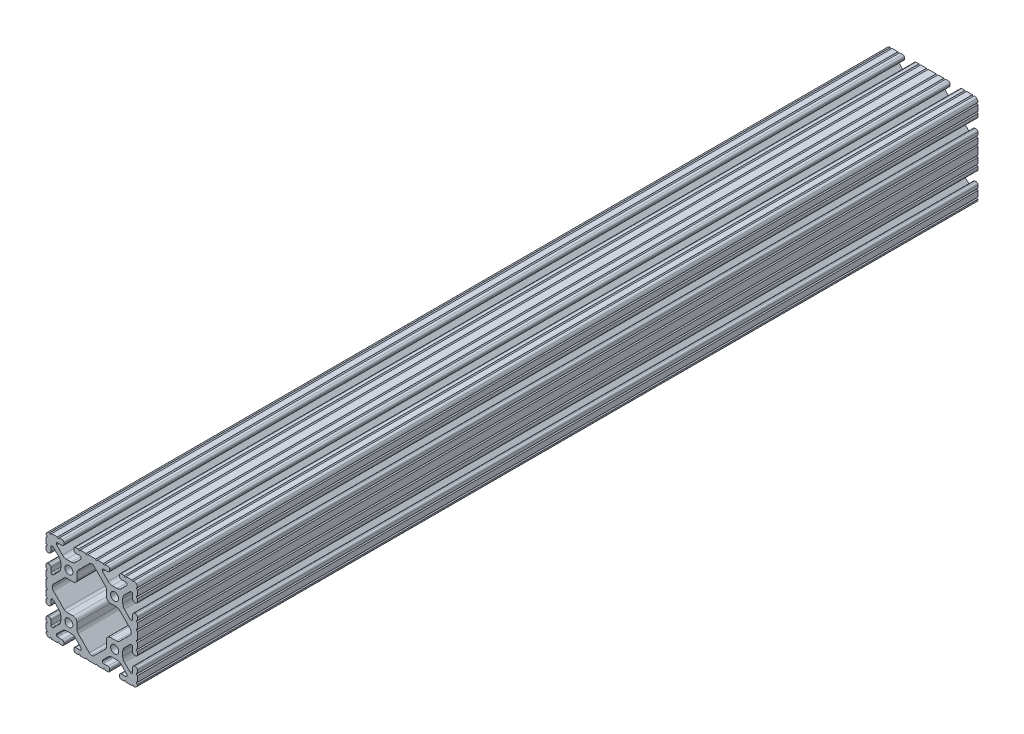
SolidWorks part; units mm, degrees
ref_plane "Front Plane" through (0, 0, 0) normal (0, 0, 1) x (1, 0, 0)
ref_plane "Top Plane" through (0, 0, 0) normal (0, 1, 0) x (1, 0, 0)
ref_plane "Right Plane" through (0, 0, 0) normal (1, 0, 0) x (0, 0, -1)
sketch "Sketch1" plane through (0, 0, 0) normal (0, 0, 1) x (1, 0, 0)
  line L0 (0, 38.1) -> (0, -38.1) construction
  line L1 (-38.1, -38.1) -> (38.1, -38.1) construction
  line L2 (-38.1, -38.1) -> (-38.1, 38.1) construction
  line L3 (-38.1, 38.1) -> (38.1, 38.1) construction
  line L4 (38.1, -38.1) -> (38.1, 38.1) construction
  line L5 (0, 38.1) -> (0, -38.1) construction
  line L6 (-38.1, 0) -> (38.1, 0) construction
  line L7 (-19.05, 19.05) -> (19.05, 19.05) construction
  line L8 (-19.05, 19.05) -> (-19.05, -19.05) construction
  line L9 (-19.05, -19.05) -> (19.05, -19.05) construction
  line L10 (19.05, 19.05) -> (19.05, -19.05) construction
  line L11 (-23.114, 38.1) -> (-23.114, -38.1) construction
  line L12 (-23.114, -38.1) -> (-14.986, 38.1) construction
  line L13 (-14.986, 38.1) -> (-14.986, -38.1) construction
  circle A0 centre (19.05, 19.05) radius 3.3274
  point P0 (0, 0)
  point P9 (0, 0)
  point P12 (-19.05, 0)
  line B0 (-11.3637, -22.8433) -> (-2.0515, -32.1555)
  line B1 (-12.2936, -15.4686) -> (-12.2936, -20.5983)
  line B2 (-20.769, -12.2936) -> (-15.4686, -12.2936)
  line B3 (-31.9021, -2.4756) -> (-23.0141, -11.3637)
  line B4 (-23.0141, 11.3637) -> (-31.9021, 2.4756)
  line B5 (-15.4686, 12.2936) -> (-20.769, 12.2936)
  line B6 (-12.2936, 20.5983) -> (-12.2936, 15.4686)
  line B7 (-2.0515, 32.1555) -> (-11.3637, 22.8433)
  line B8 (11.3637, 22.8433) -> (2.0515, 32.1555)
  line B9 (12.2936, 15.4686) -> (12.2936, 20.5983)
  line B10 (20.769, 12.2936) -> (15.4686, 12.2936)
  line B11 (31.9021, 2.4756) -> (23.0141, 11.3637)
  line B12 (23.0141, -11.3637) -> (31.9021, -2.4756)
  line B13 (15.4686, -12.2936) -> (20.769, -12.2936)
  line B14 (12.2936, -20.5983) -> (12.2936, -15.4686)
  line B15 (2.0515, -32.1555) -> (11.3637, -22.8433)
  line B16 (-4.7773, 38.1) -> (-9.6053, 38.1)
  line B17 (-11.1289, 38.1) -> (-13.4112, 38.1)
  line B18 (-14.986, 36.5252) -> (-14.986, 35.6108)
  line B19 (-13.4112, 34.036) -> (-9.652, 34.036)
  line B20 (-8.763, 33.147) -> (-8.763, 32.4935)
  line B21 (-9.0234, 31.8649) -> (-13.6907, 27.1976)
  line B22 (-17.0493, 25.8064) -> (-21.0507, 25.8064)
  line B23 (-24.4093, 27.1976) -> (-29.1002, 31.8885)
  line B24 (-29.337, 32.7207) -> (-29.337, 33.147)
  line B25 (-28.448, 34.036) -> (-24.6888, 34.036)
  line B26 (-23.114, 35.6108) -> (-23.114, 36.5252)
  line B27 (-24.6888, 38.1) -> (-27.0772, 38.1)
  line B28 (-28.6011, 38.1) -> (-33.4288, 38.1)
  line B29 (-38.1, 33.373) -> (-38.1, 28.5453)
  line B30 (-38.1, 27.0238) -> (-38.1, 24.6302)
  line B31 (-36.5252, 23.0554) -> (-35.6108, 23.0554)
  line B32 (-34.036, 24.6302) -> (-34.036, 28.448)
  line B33 (-33.147, 29.337) -> (-32.6643, 29.337)
  line B34 (-32.0357, 29.0766) -> (-27.1976, 24.2385)
  line B35 (-25.8064, 20.8799) -> (-25.8064, 17.2201)
  line B36 (-27.1976, 13.8615) -> (-31.9489, 9.1101)
  line B37 (-32.7869, 8.763) -> (-33.0603, 8.763)
  line B38 (-34.036, 9.7387) -> (-34.036, 13.4698)
  line B39 (-35.6108, 15.0446) -> (-36.5252, 15.0446)
  line B40 (-38.1, 13.4698) -> (-38.1, 11.075)
  line B41 (-38.1, 9.552) -> (-38.1, 4.7238)
  line B42 (-38.1, 3.2007) -> (-38.1, -3.2007)
  line B43 (-38.1, -4.7238) -> (-38.1, -9.552)
  line B44 (-38.1, -11.075) -> (-38.1, -13.4698)
  line B45 (-36.5252, -15.0446) -> (-35.6108, -15.0446)
  line B46 (-34.036, -13.4698) -> (-34.036, -9.7387)
  line B47 (-33.0603, -8.763) -> (-32.7869, -8.763)
  line B48 (-31.9489, -9.1101) -> (-27.1976, -13.8615)
  line B49 (-25.8064, -17.2201) -> (-25.8064, -20.8799)
  line B50 (-27.1976, -24.2385) -> (-32.0357, -29.0766)
  line B51 (-32.6643, -29.337) -> (-33.147, -29.337)
  line B52 (-34.036, -28.448) -> (-34.036, -24.6302)
  line B53 (-35.6108, -23.0554) -> (-36.5252, -23.0554)
  line B54 (-38.1, -24.6302) -> (-38.1, -27.0238)
  line B55 (-38.1, -28.5453) -> (-38.1, -33.373)
  line B56 (-33.4288, -38.1) -> (-28.6011, -38.1)
  line B57 (-27.0772, -38.1) -> (-24.6888, -38.1)
  line B58 (-23.114, -36.5252) -> (-23.114, -35.6108)
  line B59 (-24.6888, -34.036) -> (-28.448, -34.036)
  line B60 (-29.337, -33.147) -> (-29.337, -32.7207)
  line B61 (-29.1002, -31.8885) -> (-24.4093, -27.1976)
  line B62 (-21.0507, -25.8064) -> (-17.0493, -25.8064)
  line B63 (-13.6907, -27.1976) -> (-9.0234, -31.8649)
  line B64 (-8.763, -32.4935) -> (-8.763, -33.147)
  line B65 (-9.652, -34.036) -> (-13.4112, -34.036)
  line B66 (-14.986, -35.6108) -> (-14.986, -36.5252)
  line B67 (-13.4112, -38.1) -> (-11.1289, -38.1)
  line B68 (-9.6053, -38.1) -> (-4.7773, -38.1)
  line B69 (-3.2537, -38.1) -> (3.2537, -38.1)
  line B70 (4.7773, -38.1) -> (9.6053, -38.1)
  line B71 (11.1289, -38.1) -> (13.4112, -38.1)
  line B72 (14.986, -36.5252) -> (14.986, -35.6108)
  line B73 (13.4112, -34.036) -> (9.652, -34.036)
  line B74 (8.763, -33.147) -> (8.763, -32.4935)
  line B75 (9.0234, -31.8649) -> (13.6907, -27.1976)
  line B76 (17.0493, -25.8064) -> (21.0507, -25.8064)
  line B77 (24.4093, -27.1976) -> (29.1002, -31.8885)
  line B78 (29.337, -32.7207) -> (29.337, -33.147)
  line B79 (28.448, -34.036) -> (24.6888, -34.036)
  line B80 (23.114, -35.6108) -> (23.114, -36.5252)
  line B81 (24.6888, -38.1) -> (27.0772, -38.1)
  line B82 (28.6011, -38.1) -> (33.4288, -38.1)
  line B83 (38.1, -33.373) -> (38.1, -28.5453)
  line B84 (38.1, -27.0238) -> (38.1, -24.6302)
  line B85 (36.5252, -23.0554) -> (35.6108, -23.0554)
  line B86 (34.036, -24.6302) -> (34.036, -28.448)
  line B87 (33.147, -29.337) -> (32.6643, -29.337)
  line B88 (32.0357, -29.0766) -> (27.1976, -24.2385)
  line B89 (25.8064, -20.8799) -> (25.8064, -17.2201)
  line B90 (27.1976, -13.8615) -> (31.9489, -9.1101)
  line B91 (32.7869, -8.763) -> (33.0603, -8.763)
  line B92 (34.036, -9.7387) -> (34.036, -13.4698)
  line B93 (35.6108, -15.0446) -> (36.5252, -15.0446)
  line B94 (38.1, -13.4698) -> (38.1, -11.075)
  line B95 (38.1, -9.552) -> (38.1, -4.7238)
  line B96 (38.1, -3.2007) -> (38.1, 3.2007)
  line B97 (38.1, 4.7238) -> (38.1, 9.552)
  line B98 (38.1, 11.075) -> (38.1, 13.4698)
  line B99 (36.5252, 15.0446) -> (35.6108, 15.0446)
  line B100 (34.036, 13.4698) -> (34.036, 9.7387)
  line B101 (33.0603, 8.763) -> (32.7869, 8.763)
  line B102 (31.9489, 9.1101) -> (27.1976, 13.8615)
  line B103 (25.8064, 17.2201) -> (25.8064, 20.8799)
  line B104 (27.1976, 24.2385) -> (32.0357, 29.0766)
  line B105 (32.6643, 29.337) -> (33.147, 29.337)
  line B106 (34.036, 28.448) -> (34.036, 24.6302)
  line B107 (35.6108, 23.0554) -> (36.5252, 23.0554)
  line B108 (38.1, 24.6302) -> (38.1, 27.0238)
  line B109 (38.1, 28.5453) -> (38.1, 33.373)
  line B110 (33.4288, 38.1) -> (28.6011, 38.1)
  line B111 (27.0772, 38.1) -> (24.6888, 38.1)
  line B112 (23.114, 36.5252) -> (23.114, 35.6108)
  line B113 (24.6888, 34.036) -> (28.448, 34.036)
  line B114 (29.337, 33.147) -> (29.337, 32.7207)
  line B115 (29.1002, 31.8885) -> (24.4093, 27.1976)
  line B116 (21.0507, 25.8064) -> (17.0493, 25.8064)
  line B117 (13.6907, 27.1976) -> (9.0234, 31.8649)
  line B118 (8.763, 32.4935) -> (8.763, 33.147)
  line B119 (9.652, 34.036) -> (13.4112, 34.036)
  line B120 (14.986, 35.6108) -> (14.986, 36.5252)
  line B121 (13.4112, 38.1) -> (11.1289, 38.1)
  line B122 (9.6053, 38.1) -> (4.7773, 38.1)
  line B123 (3.2537, 38.1) -> (-3.2537, 38.1)
  circle B124 centre (-19.05, 19.05) radius 3.3274
  circle B125 centre (-19.05, -19.05) radius 3.3274
  circle B126 centre (19.05, -19.05) radius 3.3274
  circle B127 centre (19.05, 19.05) radius 3.3274
  arc B128 (0, -33.011) -> (2.0515, -32.1555) centre (-0.0139, -30.09) ccw
  arc B129 (-2.0515, -32.1555) -> (0, -33.011) centre (0.0139, -30.09) ccw
  arc B130 (-12.2936, -20.5983) -> (-11.3637, -22.8433) centre (-9.1186, -20.5983) ccw
  arc B131 (-12.2936, -15.4686) -> (-15.4686, -12.2936) centre (-15.4686, -15.4686) ccw
  arc B132 (-23.0141, -11.3637) -> (-20.769, -12.2936) centre (-20.769, -9.1186) ccw
  arc B133 (-32.7287, 0) -> (-31.9021, -2.4756) centre (-29.8367, -0.4102) ccw
  arc B134 (-31.9021, 2.4756) -> (-32.7287, 0) centre (-29.8367, 0.4102) ccw
  arc B135 (-20.769, 12.2936) -> (-23.0141, 11.3637) centre (-20.769, 9.1186) ccw
  arc B136 (-15.4686, 12.2936) -> (-12.2936, 15.4686) centre (-15.4686, 15.4686) ccw
  arc B137 (-11.3637, 22.8433) -> (-12.2936, 20.5983) centre (-9.1186, 20.5983) ccw
  arc B138 (0, 33.011) -> (-2.0515, 32.1555) centre (0.0139, 30.09) ccw
  arc B139 (2.0515, 32.1555) -> (0, 33.011) centre (-0.0139, 30.09) ccw
  arc B140 (12.2936, 20.5983) -> (11.3637, 22.8433) centre (9.1186, 20.5983) ccw
  arc B141 (12.2936, 15.4686) -> (15.4686, 12.2936) centre (15.4686, 15.4686) ccw
  arc B142 (23.0141, 11.3637) -> (20.769, 12.2936) centre (20.769, 9.1186) ccw
  arc B143 (32.7287, 0) -> (31.9021, 2.4756) centre (29.8367, 0.4102) ccw
  arc B144 (31.9021, -2.4756) -> (32.7287, 0) centre (29.8367, -0.4102) ccw
  arc B145 (20.769, -12.2936) -> (23.0141, -11.3637) centre (20.769, -9.1186) ccw
  arc B146 (15.4686, -12.2936) -> (12.2936, -15.4686) centre (15.4686, -15.4686) ccw
  arc B147 (11.3637, -22.8433) -> (12.2936, -20.5983) centre (9.1186, -20.5983) ccw
  arc B148 (-4.7773, 38.1) -> (-3.2537, 38.1) centre (-4.0155, 38.0824) ccw
  arc B149 (-11.1289, 38.1) -> (-9.6053, 38.1) centre (-10.3671, 38.0824) ccw
  arc B150 (-13.4112, 38.1) -> (-14.986, 36.5252) centre (-13.4112, 36.5252) ccw
  arc B151 (-14.986, 35.6108) -> (-13.4112, 34.036) centre (-13.4112, 35.6108) ccw
  arc B152 (-8.763, 33.147) -> (-9.652, 34.036) centre (-9.652, 33.147) ccw
  arc B153 (-9.0234, 31.8649) -> (-8.763, 32.4935) centre (-9.652, 32.4935) ccw
  arc B154 (-17.0493, 25.8064) -> (-13.6907, 27.1976) centre (-17.0493, 30.5562) ccw
  arc B155 (-24.4093, 27.1976) -> (-21.0507, 25.8064) centre (-21.0507, 30.5562) ccw
  arc B156 (-29.337, 32.7207) -> (-29.1002, 31.8885) centre (-28.4716, 32.5172) ccw
  arc B157 (-28.448, 34.036) -> (-29.337, 33.147) centre (-28.448, 33.147) ccw
  arc B158 (-24.6888, 34.036) -> (-23.114, 35.6108) centre (-24.6888, 35.6108) ccw
  arc B159 (-23.114, 36.5252) -> (-24.6888, 38.1) centre (-24.6888, 36.5252) ccw
  arc B160 (-28.6011, 38.1) -> (-27.0772, 38.1) centre (-27.8392, 38.0824) ccw
  arc B161 (-34.9527, 38.1) -> (-33.4288, 38.1) centre (-34.1907, 38.0824) ccw
  arc B162 (-34.9527, 38.1) -> (-37.0861, 37.1826) centre (-34.8521, 34.9266) ccw
  arc B163 (-37.0861, 37.1826) -> (-38.1, 34.8455) centre (-34.925, 34.8566) ccw
  arc B164 (-38.1, 33.373) -> (-38.1, 34.8455) centre (-37.9035, 34.1092) ccw
  arc B165 (-38.1, 27.0238) -> (-38.1, 28.5453) centre (-37.9035, 27.7845) ccw
  arc B166 (-38.1, 24.6302) -> (-36.5252, 23.0554) centre (-36.5252, 24.6302) ccw
  arc B167 (-35.6108, 23.0554) -> (-34.036, 24.6302) centre (-35.6108, 24.6302) ccw
  arc B168 (-33.147, 29.337) -> (-34.036, 28.448) centre (-33.147, 28.448) ccw
  arc B169 (-32.0357, 29.0766) -> (-32.6643, 29.337) centre (-32.6643, 28.448) ccw
  arc B170 (-25.8064, 20.8799) -> (-27.1976, 24.2385) centre (-30.5562, 20.8799) ccw
  arc B171 (-27.1976, 13.8615) -> (-25.8064, 17.2201) centre (-30.5562, 17.2201) ccw
  arc B172 (-32.7869, 8.763) -> (-31.9489, 9.1101) centre (-32.7869, 9.9481) ccw
  arc B173 (-34.036, 9.7387) -> (-33.0603, 8.763) centre (-33.0603, 9.7387) ccw
  arc B174 (-34.036, 13.4698) -> (-35.6108, 15.0446) centre (-35.6108, 13.4698) ccw
  arc B175 (-36.5252, 15.0446) -> (-38.1, 13.4698) centre (-36.5252, 13.4698) ccw
  arc B176 (-38.1, 9.552) -> (-38.1, 11.075) centre (-37.9035, 10.3135) ccw
  arc B177 (-38.1, 3.2007) -> (-38.1, 4.7238) centre (-37.9035, 3.9622) ccw
  arc B178 (-38.1, -4.7238) -> (-38.1, -3.2007) centre (-37.9035, -3.9622) ccw
  arc B179 (-38.1, -11.075) -> (-38.1, -9.552) centre (-37.9035, -10.3135) ccw
  arc B180 (-38.1, -13.4698) -> (-36.5252, -15.0446) centre (-36.5252, -13.4698) ccw
  arc B181 (-35.6108, -15.0446) -> (-34.036, -13.4698) centre (-35.6108, -13.4698) ccw
  arc B182 (-33.0603, -8.763) -> (-34.036, -9.7387) centre (-33.0603, -9.7387) ccw
  arc B183 (-31.9489, -9.1101) -> (-32.7869, -8.763) centre (-32.7869, -9.9481) ccw
  arc B184 (-25.8064, -17.2201) -> (-27.1976, -13.8615) centre (-30.5562, -17.2201) ccw
  arc B185 (-27.1976, -24.2385) -> (-25.8064, -20.8799) centre (-30.5562, -20.8799) ccw
  arc B186 (-32.6643, -29.337) -> (-32.0357, -29.0766) centre (-32.6643, -28.448) ccw
  arc B187 (-34.036, -28.448) -> (-33.147, -29.337) centre (-33.147, -28.448) ccw
  arc B188 (-34.036, -24.6302) -> (-35.6108, -23.0554) centre (-35.6108, -24.6302) ccw
  arc B189 (-36.5252, -23.0554) -> (-38.1, -24.6302) centre (-36.5252, -24.6302) ccw
  arc B190 (-38.1, -28.5453) -> (-38.1, -27.0238) centre (-37.9035, -27.7845) ccw
  arc B191 (-38.1, -34.8455) -> (-38.1, -33.373) centre (-37.9035, -34.1092) ccw
  arc B192 (-38.1, -34.8455) -> (-37.0861, -37.1826) centre (-34.925, -34.8566) ccw
  arc B193 (-37.0861, -37.1826) -> (-34.9527, -38.1) centre (-34.8521, -34.9266) ccw
  arc B194 (-33.4288, -38.1) -> (-34.9527, -38.1) centre (-34.1907, -38.0824) ccw
  arc B195 (-27.0772, -38.1) -> (-28.6011, -38.1) centre (-27.8392, -38.0824) ccw
  arc B196 (-24.6888, -38.1) -> (-23.114, -36.5252) centre (-24.6888, -36.5252) ccw
  arc B197 (-23.114, -35.6108) -> (-24.6888, -34.036) centre (-24.6888, -35.6108) ccw
  arc B198 (-29.337, -33.147) -> (-28.448, -34.036) centre (-28.448, -33.147) ccw
  arc B199 (-29.1002, -31.8885) -> (-29.337, -32.7207) centre (-28.4716, -32.5172) ccw
  arc B200 (-21.0507, -25.8064) -> (-24.4093, -27.1976) centre (-21.0507, -30.5562) ccw
  arc B201 (-13.6907, -27.1976) -> (-17.0493, -25.8064) centre (-17.0493, -30.5562) ccw
  arc B202 (-8.763, -32.4935) -> (-9.0234, -31.8649) centre (-9.652, -32.4935) ccw
  arc B203 (-9.652, -34.036) -> (-8.763, -33.147) centre (-9.652, -33.147) ccw
  arc B204 (-13.4112, -34.036) -> (-14.986, -35.6108) centre (-13.4112, -35.6108) ccw
  arc B205 (-14.986, -36.5252) -> (-13.4112, -38.1) centre (-13.4112, -36.5252) ccw
  arc B206 (-9.6053, -38.1) -> (-11.1289, -38.1) centre (-10.3671, -38.0824) ccw
  arc B207 (-3.2537, -38.1) -> (-4.7773, -38.1) centre (-4.0155, -38.0824) ccw
  arc B208 (4.7773, -38.1) -> (3.2537, -38.1) centre (4.0155, -38.0824) ccw
  arc B209 (11.1289, -38.1) -> (9.6053, -38.1) centre (10.3671, -38.0824) ccw
  arc B210 (13.4112, -38.1) -> (14.986, -36.5252) centre (13.4112, -36.5252) ccw
  arc B211 (14.986, -35.6108) -> (13.4112, -34.036) centre (13.4112, -35.6108) ccw
  arc B212 (8.763, -33.147) -> (9.652, -34.036) centre (9.652, -33.147) ccw
  arc B213 (9.0234, -31.8649) -> (8.763, -32.4935) centre (9.652, -32.4935) ccw
  arc B214 (17.0493, -25.8064) -> (13.6907, -27.1976) centre (17.0493, -30.5562) ccw
  arc B215 (24.4093, -27.1976) -> (21.0507, -25.8064) centre (21.0507, -30.5562) ccw
  arc B216 (29.337, -32.7207) -> (29.1002, -31.8885) centre (28.4716, -32.5172) ccw
  arc B217 (28.448, -34.036) -> (29.337, -33.147) centre (28.448, -33.147) ccw
  arc B218 (24.6888, -34.036) -> (23.114, -35.6108) centre (24.6888, -35.6108) ccw
  arc B219 (23.114, -36.5252) -> (24.6888, -38.1) centre (24.6888, -36.5252) ccw
  arc B220 (28.6011, -38.1) -> (27.0772, -38.1) centre (27.8392, -38.0824) ccw
  arc B221 (34.9527, -38.1) -> (33.4288, -38.1) centre (34.1907, -38.0824) ccw
  arc B222 (34.9527, -38.1) -> (37.0861, -37.1826) centre (34.8521, -34.9266) ccw
  arc B223 (37.0861, -37.1826) -> (38.1, -34.8455) centre (34.925, -34.8566) ccw
  arc B224 (38.1, -33.373) -> (38.1, -34.8455) centre (37.9035, -34.1092) ccw
  arc B225 (38.1, -27.0238) -> (38.1, -28.5453) centre (37.9035, -27.7845) ccw
  arc B226 (38.1, -24.6302) -> (36.5252, -23.0554) centre (36.5252, -24.6302) ccw
  arc B227 (35.6108, -23.0554) -> (34.036, -24.6302) centre (35.6108, -24.6302) ccw
  arc B228 (33.147, -29.337) -> (34.036, -28.448) centre (33.147, -28.448) ccw
  arc B229 (32.0357, -29.0766) -> (32.6643, -29.337) centre (32.6643, -28.448) ccw
  arc B230 (25.8064, -20.8799) -> (27.1976, -24.2385) centre (30.5562, -20.8799) ccw
  arc B231 (27.1976, -13.8615) -> (25.8064, -17.2201) centre (30.5562, -17.2201) ccw
  arc B232 (32.7869, -8.763) -> (31.9489, -9.1101) centre (32.7869, -9.9481) ccw
  arc B233 (34.036, -9.7387) -> (33.0603, -8.763) centre (33.0603, -9.7387) ccw
  arc B234 (34.036, -13.4698) -> (35.6108, -15.0446) centre (35.6108, -13.4698) ccw
  arc B235 (36.5252, -15.0446) -> (38.1, -13.4698) centre (36.5252, -13.4698) ccw
  arc B236 (38.1, -9.552) -> (38.1, -11.075) centre (37.9035, -10.3135) ccw
  arc B237 (38.1, -3.2007) -> (38.1, -4.7238) centre (37.9035, -3.9622) ccw
  arc B238 (38.1, 4.7238) -> (38.1, 3.2007) centre (37.9035, 3.9622) ccw
  arc B239 (38.1, 11.075) -> (38.1, 9.552) centre (37.9035, 10.3135) ccw
  arc B240 (38.1, 13.4698) -> (36.5252, 15.0446) centre (36.5252, 13.4698) ccw
  arc B241 (35.6108, 15.0446) -> (34.036, 13.4698) centre (35.6108, 13.4698) ccw
  arc B242 (33.0603, 8.763) -> (34.036, 9.7387) centre (33.0603, 9.7387) ccw
  arc B243 (31.9489, 9.1101) -> (32.7869, 8.763) centre (32.7869, 9.9481) ccw
  arc B244 (25.8064, 17.2201) -> (27.1976, 13.8615) centre (30.5562, 17.2201) ccw
  arc B245 (27.1976, 24.2385) -> (25.8064, 20.8799) centre (30.5562, 20.8799) ccw
  arc B246 (32.6643, 29.337) -> (32.0357, 29.0766) centre (32.6643, 28.448) ccw
  arc B247 (34.036, 28.448) -> (33.147, 29.337) centre (33.147, 28.448) ccw
  arc B248 (34.036, 24.6302) -> (35.6108, 23.0554) centre (35.6108, 24.6302) ccw
  arc B249 (36.5252, 23.0554) -> (38.1, 24.6302) centre (36.5252, 24.6302) ccw
  arc B250 (38.1, 28.5453) -> (38.1, 27.0238) centre (37.9035, 27.7845) ccw
  arc B251 (38.1, 34.8455) -> (38.1, 33.373) centre (37.9035, 34.1092) ccw
  arc B252 (38.1, 34.8455) -> (37.0861, 37.1826) centre (34.925, 34.8566) ccw
  arc B253 (37.0861, 37.1826) -> (34.9527, 38.1) centre (34.8521, 34.9266) ccw
  arc B254 (33.4288, 38.1) -> (34.9527, 38.1) centre (34.1907, 38.0824) ccw
  arc B255 (27.0772, 38.1) -> (28.6011, 38.1) centre (27.8392, 38.0824) ccw
  arc B256 (24.6888, 38.1) -> (23.114, 36.5252) centre (24.6888, 36.5252) ccw
  arc B257 (23.114, 35.6108) -> (24.6888, 34.036) centre (24.6888, 35.6108) ccw
  arc B258 (29.337, 33.147) -> (28.448, 34.036) centre (28.448, 33.147) ccw
  arc B259 (29.1002, 31.8885) -> (29.337, 32.7207) centre (28.4716, 32.5172) ccw
  arc B260 (21.0507, 25.8064) -> (24.4093, 27.1976) centre (21.0507, 30.5562) ccw
  arc B261 (13.6907, 27.1976) -> (17.0493, 25.8064) centre (17.0493, 30.5562) ccw
  arc B262 (8.763, 32.4935) -> (9.0234, 31.8649) centre (9.652, 32.4935) ccw
  arc B263 (9.652, 34.036) -> (8.763, 33.147) centre (9.652, 33.147) ccw
  arc B264 (13.4112, 34.036) -> (14.986, 35.6108) centre (13.4112, 35.6108) ccw
  arc B265 (14.986, 36.5252) -> (13.4112, 38.1) centre (13.4112, 36.5252) ccw
  arc B266 (9.6053, 38.1) -> (11.1289, 38.1) centre (10.3671, 38.0824) ccw
  arc B267 (3.2537, 38.1) -> (4.7773, 38.1) centre (4.0155, 38.0824) ccw
  dimension "Center Hole Diameter" = 6.6548
  dimension "Rail Width" = 76.2
  dimension "Rail Height" = 76.2
  dimension "T-Slot Width" = 8.128
sketch_block_instance "Block1-1"
sketch_block "Block1"
sketch "Sketch2" plane through (0, 0, 0) normal (1, 0, 0) x (0, 0, -1)
  line L0 (-350, 0) -> (350, 0) construction
  line L1 (-350, 38.1) -> (-350, -38.1) construction
  line L2 (-350, -38.1) -> (350, -38.1) construction
  line L3 (350, -38.1) -> (350, 38.1) construction
  line L4 (-248.4, 0) -> (-248.4, 38.1) construction
  line L5 (-248.4, 38.1) -> (248.4, 38.1) construction
  line L6 (248.4, 38.1) -> (248.4, 0) construction
  point P5 (248.4, 0)
  point P10 (-248.4, 0)
  dimension "D1" = 101.6
  dimension "Length" = 700
  dimension "D2" = 101.6
sketch "Sketch3" plane through (0, 0, 0) normal (0, 0, 1) x (1, 0, 0)
  line L0 (-11.3637, -22.8433) -> (-2.0515, -32.1555) construction
  line L1 (-12.2936, -15.4686) -> (-12.2936, -20.5983) construction
  line L2 (-20.769, -12.2936) -> (-15.4686, -12.2936) construction
  line L3 (-31.9021, -2.4756) -> (-23.0141, -11.3637) construction
  line L4 (-23.0141, 11.3637) -> (-31.9021, 2.4756) construction
  line L5 (-15.4686, 12.2936) -> (-20.769, 12.2936) construction
  line L6 (-12.2936, 20.5983) -> (-12.2936, 15.4686) construction
  line L7 (-2.0515, 32.1555) -> (-11.3637, 22.8433) construction
  line L8 (11.3637, 22.8433) -> (2.0515, 32.1555) construction
  line L9 (12.2936, 15.4686) -> (12.2936, 20.5983) construction
  line L10 (20.769, 12.2936) -> (15.4686, 12.2936) construction
  line L11 (31.9021, 2.4756) -> (23.0141, 11.3637) construction
  line L12 (23.0141, -11.3637) -> (31.9021, -2.4756) construction
  line L13 (15.4686, -12.2936) -> (20.769, -12.2936) construction
  line L14 (12.2936, -20.5983) -> (12.2936, -15.4686) construction
  line L15 (2.0515, -32.1555) -> (11.3637, -22.8433) construction
  line L16 (34.036, 28.448) -> (34.036, 24.6302) construction
  line L17 (35.6108, 23.0554) -> (36.5252, 23.0554) construction
  line L18 (38.1, 24.6302) -> (38.1, 27.0238) construction
  line L19 (38.1, 28.5453) -> (38.1, 33.373) construction
  line L20 (33.4288, 38.1) -> (28.6011, 38.1) construction
  line L21 (27.0772, 38.1) -> (24.6888, 38.1) construction
  line L22 (23.114, 36.5252) -> (23.114, 35.6108) construction
  line L23 (24.6888, 34.036) -> (28.448, 34.036) construction
  line L24 (29.337, 33.147) -> (29.337, 32.7207) construction
  line L25 (29.1002, 31.8885) -> (24.4093, 27.1976) construction
  line L26 (21.0507, 25.8064) -> (17.0493, 25.8064) construction
  line L27 (13.6907, 27.1976) -> (9.0234, 31.8649) construction
  line L28 (8.763, 32.4935) -> (8.763, 33.147) construction
  line L29 (9.652, 34.036) -> (13.4112, 34.036) construction
  line L30 (14.986, 35.6108) -> (14.986, 36.5252) construction
  line L31 (13.4112, 38.1) -> (11.1289, 38.1) construction
  line L32 (9.6053, 38.1) -> (4.7773, 38.1) construction
  line L33 (3.2537, 38.1) -> (-3.2537, 38.1) construction
  line L34 (-4.7773, 38.1) -> (-9.6053, 38.1) construction
  line L35 (-11.1289, 38.1) -> (-13.4112, 38.1) construction
  line L36 (-14.986, 36.5252) -> (-14.986, 35.6108) construction
  line L37 (-13.4112, 34.036) -> (-9.652, 34.036) construction
  line L38 (-8.763, 33.147) -> (-8.763, 32.4935) construction
  line L39 (-9.0234, 31.8649) -> (-13.6907, 27.1976) construction
  line L40 (-17.0493, 25.8064) -> (-21.0507, 25.8064) construction
  line L41 (-24.4093, 27.1976) -> (-29.1002, 31.8885) construction
  line L42 (-29.337, 32.7207) -> (-29.337, 33.147) construction
  line L43 (-28.448, 34.036) -> (-24.6888, 34.036) construction
  line L44 (-23.114, 35.6108) -> (-23.114, 36.5252) construction
  line L45 (-24.6888, 38.1) -> (-27.0772, 38.1) construction
  line L46 (-28.6011, 38.1) -> (-33.4288, 38.1) construction
  line L47 (-38.1, 33.373) -> (-38.1, 28.5453) construction
  line L48 (-38.1, 27.0238) -> (-38.1, 24.6302) construction
  line L49 (-36.5252, 23.0554) -> (-35.6108, 23.0554) construction
  line L50 (-34.036, 24.6302) -> (-34.036, 28.448) construction
  line L51 (-33.147, 29.337) -> (-32.6643, 29.337) construction
  line L52 (-32.0357, 29.0766) -> (-27.1976, 24.2385) construction
  line L53 (-25.8064, 20.8799) -> (-25.8064, 17.2201) construction
  line L54 (-27.1976, 13.8615) -> (-31.9489, 9.1101) construction
  line L55 (-32.7869, 8.763) -> (-33.0603, 8.763) construction
  line L56 (-34.036, 9.7387) -> (-34.036, 13.4698) construction
  line L57 (-35.6108, 15.0446) -> (-36.5252, 15.0446) construction
  line L58 (-38.1, 13.4698) -> (-38.1, 11.075) construction
  line L59 (-38.1, 9.552) -> (-38.1, 4.7238) construction
  line L60 (-38.1, 3.2007) -> (-38.1, -3.2007) construction
  line L61 (-38.1, -4.7238) -> (-38.1, -9.552) construction
  line L62 (-38.1, -11.075) -> (-38.1, -13.4698) construction
  line L63 (-36.5252, -15.0446) -> (-35.6108, -15.0446) construction
  line L64 (-34.036, -13.4698) -> (-34.036, -9.7387) construction
  line L65 (-33.0603, -8.763) -> (-32.7869, -8.763) construction
  line L66 (-31.9489, -9.1101) -> (-27.1976, -13.8615) construction
  line L67 (-25.8064, -17.2201) -> (-25.8064, -20.8799) construction
  line L68 (-27.1976, -24.2385) -> (-32.0357, -29.0766) construction
  line L69 (-32.6643, -29.337) -> (-33.147, -29.337) construction
  line L70 (-34.036, -28.448) -> (-34.036, -24.6302) construction
  line L71 (-35.6108, -23.0554) -> (-36.5252, -23.0554) construction
  line L72 (-38.1, -24.6302) -> (-38.1, -27.0238) construction
  line L73 (-38.1, -28.5453) -> (-38.1, -33.373) construction
  line L74 (-33.4288, -38.1) -> (-28.6011, -38.1) construction
  line L75 (-27.0772, -38.1) -> (-24.6888, -38.1) construction
  line L76 (-23.114, -36.5252) -> (-23.114, -35.6108) construction
  line L77 (-24.6888, -34.036) -> (-28.448, -34.036) construction
  line L78 (-29.337, -33.147) -> (-29.337, -32.7207) construction
  line L79 (-29.1002, -31.8885) -> (-24.4093, -27.1976) construction
  line L80 (-21.0507, -25.8064) -> (-17.0493, -25.8064) construction
  line L81 (-13.6907, -27.1976) -> (-9.0234, -31.8649) construction
  line L82 (-8.763, -32.4935) -> (-8.763, -33.147) construction
  line L83 (-9.652, -34.036) -> (-13.4112, -34.036) construction
  line L84 (-14.986, -35.6108) -> (-14.986, -36.5252) construction
  line L85 (-13.4112, -38.1) -> (-11.1289, -38.1) construction
  line L86 (-9.6053, -38.1) -> (-4.7773, -38.1) construction
  line L87 (-3.2537, -38.1) -> (3.2537, -38.1) construction
  line L88 (4.7773, -38.1) -> (9.6053, -38.1) construction
  line L89 (11.1289, -38.1) -> (13.4112, -38.1) construction
  line L90 (14.986, -36.5252) -> (14.986, -35.6108) construction
  line L91 (13.4112, -34.036) -> (9.652, -34.036) construction
  line L92 (8.763, -33.147) -> (8.763, -32.4935) construction
  line L93 (9.0234, -31.8649) -> (13.6907, -27.1976) construction
  line L94 (17.0493, -25.8064) -> (21.0507, -25.8064) construction
  line L95 (24.4093, -27.1976) -> (29.1002, -31.8885) construction
  line L96 (29.337, -32.7207) -> (29.337, -33.147) construction
  line L97 (28.448, -34.036) -> (24.6888, -34.036) construction
  line L98 (23.114, -35.6108) -> (23.114, -36.5252) construction
  line L99 (24.6888, -38.1) -> (27.0772, -38.1) construction
  line L100 (28.6011, -38.1) -> (33.4288, -38.1) construction
  line L101 (38.1, -33.373) -> (38.1, -28.5453) construction
  line L102 (38.1, -27.0238) -> (38.1, -24.6302) construction
  line L103 (36.5252, -23.0554) -> (35.6108, -23.0554) construction
  line L104 (34.036, -24.6302) -> (34.036, -28.448) construction
  line L105 (33.147, -29.337) -> (32.6643, -29.337) construction
  line L106 (32.0357, -29.0766) -> (27.1976, -24.2385) construction
  line L107 (25.8064, -20.8799) -> (25.8064, -17.2201) construction
  line L108 (27.1976, -13.8615) -> (31.9489, -9.1101) construction
  line L109 (32.7869, -8.763) -> (33.0603, -8.763) construction
  line L110 (34.036, -9.7387) -> (34.036, -13.4698) construction
  line L111 (35.6108, -15.0446) -> (36.5252, -15.0446) construction
  line L112 (38.1, -13.4698) -> (38.1, -11.075) construction
  line L113 (38.1, -9.552) -> (38.1, -4.7238) construction
  line L114 (38.1, -3.2007) -> (38.1, 3.2007) construction
  line L115 (38.1, 4.7238) -> (38.1, 9.552) construction
  line L116 (38.1, 11.075) -> (38.1, 13.4698) construction
  line L117 (36.5252, 15.0446) -> (35.6108, 15.0446) construction
  line L118 (34.036, 13.4698) -> (34.036, 9.7387) construction
  line L119 (33.0603, 8.763) -> (32.7869, 8.763) construction
  line L120 (31.9489, 9.1101) -> (27.1976, 13.8615) construction
  line L121 (25.8064, 17.2201) -> (25.8064, 20.8799) construction
  line L122 (27.1976, 24.2385) -> (32.0357, 29.0766) construction
  line L123 (32.6643, 29.337) -> (33.147, 29.337) construction
  line L124 (-11.3637, -22.8433) -> (-2.0515, -32.1555)
  line L125 (-12.2936, -15.4686) -> (-12.2936, -20.5983)
  line L126 (-20.769, -12.2936) -> (-15.4686, -12.2936)
  line L127 (-31.9021, -2.4756) -> (-23.0141, -11.3637)
  line L128 (-23.0141, 11.3637) -> (-31.9021, 2.4756)
  line L129 (-15.4686, 12.2936) -> (-20.769, 12.2936)
  line L130 (-12.2936, 20.5983) -> (-12.2936, 15.4686)
  line L131 (-2.0515, 32.1555) -> (-11.3637, 22.8433)
  line L132 (11.3637, 22.8433) -> (2.0515, 32.1555)
  line L133 (12.2936, 15.4686) -> (12.2936, 20.5983)
  line L134 (20.769, 12.2936) -> (15.4686, 12.2936)
  line L135 (31.9021, 2.4756) -> (23.0141, 11.3637)
  line L136 (23.0141, -11.3637) -> (31.9021, -2.4756)
  line L137 (15.4686, -12.2936) -> (20.769, -12.2936)
  line L138 (12.2936, -20.5983) -> (12.2936, -15.4686)
  line L139 (2.0515, -32.1555) -> (11.3637, -22.8433)
  line L140 (34.036, 28.448) -> (34.036, 24.6302)
  line L141 (35.6108, 23.0554) -> (36.5252, 23.0554)
  line L142 (38.1, 24.6302) -> (38.1, 27.0238)
  line L143 (38.1, 28.5453) -> (38.1, 33.373)
  line L144 (33.4288, 38.1) -> (28.6011, 38.1)
  line L145 (27.0772, 38.1) -> (24.6888, 38.1)
  line L146 (23.114, 36.5252) -> (23.114, 35.6108)
  line L147 (24.6888, 34.036) -> (28.448, 34.036)
  line L148 (29.337, 33.147) -> (29.337, 32.7207)
  line L149 (29.1002, 31.8885) -> (24.4093, 27.1976)
  line L150 (21.0507, 25.8064) -> (17.0493, 25.8064)
  line L151 (13.6907, 27.1976) -> (9.0234, 31.8649)
  line L152 (8.763, 32.4935) -> (8.763, 33.147)
  line L153 (9.652, 34.036) -> (13.4112, 34.036)
  line L154 (14.986, 35.6108) -> (14.986, 36.5252)
  line L155 (13.4112, 38.1) -> (11.1289, 38.1)
  line L156 (9.6053, 38.1) -> (4.7773, 38.1)
  line L157 (3.2537, 38.1) -> (-3.2537, 38.1)
  line L158 (-4.7773, 38.1) -> (-9.6053, 38.1)
  line L159 (-11.1289, 38.1) -> (-13.4112, 38.1)
  line L160 (-14.986, 36.5252) -> (-14.986, 35.6108)
  line L161 (-13.4112, 34.036) -> (-9.652, 34.036)
  line L162 (-8.763, 33.147) -> (-8.763, 32.4935)
  line L163 (-9.0234, 31.8649) -> (-13.6907, 27.1976)
  line L164 (-17.0493, 25.8064) -> (-21.0507, 25.8064)
  line L165 (-24.4093, 27.1976) -> (-29.1002, 31.8885)
  line L166 (-29.337, 32.7207) -> (-29.337, 33.147)
  line L167 (-28.448, 34.036) -> (-24.6888, 34.036)
  line L168 (-23.114, 35.6108) -> (-23.114, 36.5252)
  line L169 (-24.6888, 38.1) -> (-27.0772, 38.1)
  line L170 (-28.6011, 38.1) -> (-33.4288, 38.1)
  line L171 (-38.1, 33.373) -> (-38.1, 28.5453)
  line L172 (-38.1, 27.0238) -> (-38.1, 24.6302)
  line L173 (-36.5252, 23.0554) -> (-35.6108, 23.0554)
  line L174 (-34.036, 24.6302) -> (-34.036, 28.448)
  line L175 (-33.147, 29.337) -> (-32.6643, 29.337)
  line L176 (-32.0357, 29.0766) -> (-27.1976, 24.2385)
  line L177 (-25.8064, 20.8799) -> (-25.8064, 17.2201)
  line L178 (-27.1976, 13.8615) -> (-31.9489, 9.1101)
  line L179 (-32.7869, 8.763) -> (-33.0603, 8.763)
  line L180 (-34.036, 9.7387) -> (-34.036, 13.4698)
  line L181 (-35.6108, 15.0446) -> (-36.5252, 15.0446)
  line L182 (-38.1, 13.4698) -> (-38.1, 11.075)
  line L183 (-38.1, 9.552) -> (-38.1, 4.7238)
  line L184 (-38.1, 3.2007) -> (-38.1, -3.2007)
  line L185 (-38.1, -4.7238) -> (-38.1, -9.552)
  line L186 (-38.1, -11.075) -> (-38.1, -13.4698)
  line L187 (-36.5252, -15.0446) -> (-35.6108, -15.0446)
  line L188 (-34.036, -13.4698) -> (-34.036, -9.7387)
  line L189 (-33.0603, -8.763) -> (-32.7869, -8.763)
  line L190 (-31.9489, -9.1101) -> (-27.1976, -13.8615)
  line L191 (-25.8064, -17.2201) -> (-25.8064, -20.8799)
  line L192 (-27.1976, -24.2385) -> (-32.0357, -29.0766)
  line L193 (-32.6643, -29.337) -> (-33.147, -29.337)
  line L194 (-34.036, -28.448) -> (-34.036, -24.6302)
  line L195 (-35.6108, -23.0554) -> (-36.5252, -23.0554)
  line L196 (-38.1, -24.6302) -> (-38.1, -27.0238)
  line L197 (-38.1, -28.5453) -> (-38.1, -33.373)
  line L198 (-33.4288, -38.1) -> (-28.6011, -38.1)
  line L199 (-27.0772, -38.1) -> (-24.6888, -38.1)
  line L200 (-23.114, -36.5252) -> (-23.114, -35.6108)
  line L201 (-24.6888, -34.036) -> (-28.448, -34.036)
  line L202 (-29.337, -33.147) -> (-29.337, -32.7207)
  line L203 (-29.1002, -31.8885) -> (-24.4093, -27.1976)
  line L204 (-21.0507, -25.8064) -> (-17.0493, -25.8064)
  line L205 (-13.6907, -27.1976) -> (-9.0234, -31.8649)
  line L206 (-8.763, -32.4935) -> (-8.763, -33.147)
  line L207 (-9.652, -34.036) -> (-13.4112, -34.036)
  line L208 (-14.986, -35.6108) -> (-14.986, -36.5252)
  line L209 (-13.4112, -38.1) -> (-11.1289, -38.1)
  line L210 (-9.6053, -38.1) -> (-4.7773, -38.1)
  line L211 (-3.2537, -38.1) -> (3.2537, -38.1)
  line L212 (4.7773, -38.1) -> (9.6053, -38.1)
  line L213 (11.1289, -38.1) -> (13.4112, -38.1)
  line L214 (14.986, -36.5252) -> (14.986, -35.6108)
  line L215 (13.4112, -34.036) -> (9.652, -34.036)
  line L216 (8.763, -33.147) -> (8.763, -32.4935)
  line L217 (9.0234, -31.8649) -> (13.6907, -27.1976)
  line L218 (17.0493, -25.8064) -> (21.0507, -25.8064)
  line L219 (24.4093, -27.1976) -> (29.1002, -31.8885)
  line L220 (29.337, -32.7207) -> (29.337, -33.147)
  line L221 (28.448, -34.036) -> (24.6888, -34.036)
  line L222 (23.114, -35.6108) -> (23.114, -36.5252)
  line L223 (24.6888, -38.1) -> (27.0772, -38.1)
  line L224 (28.6011, -38.1) -> (33.4288, -38.1)
  line L225 (38.1, -33.373) -> (38.1, -28.5453)
  line L226 (38.1, -27.0238) -> (38.1, -24.6302)
  line L227 (36.5252, -23.0554) -> (35.6108, -23.0554)
  line L228 (34.036, -24.6302) -> (34.036, -28.448)
  line L229 (33.147, -29.337) -> (32.6643, -29.337)
  line L230 (32.0357, -29.0766) -> (27.1976, -24.2385)
  line L231 (25.8064, -20.8799) -> (25.8064, -17.2201)
  line L232 (27.1976, -13.8615) -> (31.9489, -9.1101)
  line L233 (32.7869, -8.763) -> (33.0603, -8.763)
  line L234 (34.036, -9.7387) -> (34.036, -13.4698)
  line L235 (35.6108, -15.0446) -> (36.5252, -15.0446)
  line L236 (38.1, -13.4698) -> (38.1, -11.075)
  line L237 (38.1, -9.552) -> (38.1, -4.7238)
  line L238 (38.1, -3.2007) -> (38.1, 3.2007)
  line L239 (38.1, 4.7238) -> (38.1, 9.552)
  line L240 (38.1, 11.075) -> (38.1, 13.4698)
  line L241 (36.5252, 15.0446) -> (35.6108, 15.0446)
  line L242 (34.036, 13.4698) -> (34.036, 9.7387)
  line L243 (33.0603, 8.763) -> (32.7869, 8.763)
  line L244 (31.9489, 9.1101) -> (27.1976, 13.8615)
  line L245 (25.8064, 17.2201) -> (25.8064, 20.8799)
  line L246 (27.1976, 24.2385) -> (32.0357, 29.0766)
  line L247 (32.6643, 29.337) -> (33.147, 29.337)
  arc A0 (-2.0515, -32.1555) -> (0, -33.011) centre (0.0139, -30.09) ccw construction
  circle A1 centre (19.05, 19.05) radius 3.3274
  circle A2 centre (19.05, 19.05) radius 3.3274
  arc A3 (-12.2936, -20.5983) -> (-11.3637, -22.8433) centre (-9.1186, -20.5983) ccw construction
  arc A4 (-12.2936, -15.4686) -> (-15.4686, -12.2936) centre (-15.4686, -15.4686) ccw construction
  arc A5 (-23.0141, -11.3637) -> (-20.769, -12.2936) centre (-20.769, -9.1186) ccw construction
  arc A6 (-32.7287, 0) -> (-31.9021, -2.4756) centre (-29.8367, -0.4102) ccw construction
  arc A7 (-31.9021, 2.4756) -> (-32.7287, 0) centre (-29.8367, 0.4102) ccw construction
  arc A8 (-20.769, 12.2936) -> (-23.0141, 11.3637) centre (-20.769, 9.1186) ccw construction
  arc A9 (-15.4686, 12.2936) -> (-12.2936, 15.4686) centre (-15.4686, 15.4686) ccw construction
  arc A10 (-11.3637, 22.8433) -> (-12.2936, 20.5983) centre (-9.1186, 20.5983) ccw construction
  arc A11 (0, 33.011) -> (-2.0515, 32.1555) centre (0.0139, 30.09) ccw construction
  arc A12 (2.0515, 32.1555) -> (0, 33.011) centre (-0.0139, 30.09) ccw construction
  arc A13 (12.2936, 20.5983) -> (11.3637, 22.8433) centre (9.1186, 20.5983) ccw construction
  arc A14 (12.2936, 15.4686) -> (15.4686, 12.2936) centre (15.4686, 15.4686) ccw construction
  arc A15 (23.0141, 11.3637) -> (20.769, 12.2936) centre (20.769, 9.1186) ccw construction
  arc A16 (32.7287, 0) -> (31.9021, 2.4756) centre (29.8367, 0.4102) ccw construction
  arc A17 (31.9021, -2.4756) -> (32.7287, 0) centre (29.8367, -0.4102) ccw construction
  arc A18 (20.769, -12.2936) -> (23.0141, -11.3637) centre (20.769, -9.1186) ccw construction
  arc A19 (15.4686, -12.2936) -> (12.2936, -15.4686) centre (15.4686, -15.4686) ccw construction
  arc A20 (11.3637, -22.8433) -> (12.2936, -20.5983) centre (9.1186, -20.5983) ccw construction
  arc A21 (0, -33.011) -> (2.0515, -32.1555) centre (-0.0139, -30.09) ccw construction
  circle A22 centre (-19.05, 19.05) radius 3.3274 construction
  circle A23 centre (19.05, -19.05) radius 3.3274 construction
  circle A24 centre (-19.05, -19.05) radius 3.3274 construction
  circle A25 centre (19.05, 19.05) radius 3.3274 construction
  arc A26 (34.036, 24.6302) -> (35.6108, 23.0554) centre (35.6108, 24.6302) ccw construction
  arc A27 (36.5252, 23.0554) -> (38.1, 24.6302) centre (36.5252, 24.6302) ccw construction
  arc A28 (38.1, 28.5453) -> (38.1, 27.0238) centre (37.9035, 27.7845) ccw construction
  arc A29 (38.1, 34.8455) -> (38.1, 33.373) centre (37.9035, 34.1092) ccw construction
  arc A30 (38.1, 34.8455) -> (37.0861, 37.1826) centre (34.925, 34.8566) ccw construction
  arc A31 (37.0861, 37.1826) -> (34.9527, 38.1) centre (34.8521, 34.9266) ccw construction
  arc A32 (33.4288, 38.1) -> (34.9527, 38.1) centre (34.1907, 38.0824) ccw construction
  arc A33 (27.0772, 38.1) -> (28.6011, 38.1) centre (27.8392, 38.0824) ccw construction
  arc A34 (24.6888, 38.1) -> (23.114, 36.5252) centre (24.6888, 36.5252) ccw construction
  arc A35 (23.114, 35.6108) -> (24.6888, 34.036) centre (24.6888, 35.6108) ccw construction
  arc A36 (29.337, 33.147) -> (28.448, 34.036) centre (28.448, 33.147) ccw construction
  arc A37 (29.1002, 31.8885) -> (29.337, 32.7207) centre (28.4716, 32.5172) ccw construction
  arc A38 (21.0507, 25.8064) -> (24.4093, 27.1976) centre (21.0507, 30.5562) ccw construction
  arc A39 (13.6907, 27.1976) -> (17.0493, 25.8064) centre (17.0493, 30.5562) ccw construction
  arc A40 (8.763, 32.4935) -> (9.0234, 31.8649) centre (9.652, 32.4935) ccw construction
  arc A41 (9.652, 34.036) -> (8.763, 33.147) centre (9.652, 33.147) ccw construction
  arc A42 (13.4112, 34.036) -> (14.986, 35.6108) centre (13.4112, 35.6108) ccw construction
  arc A43 (14.986, 36.5252) -> (13.4112, 38.1) centre (13.4112, 36.5252) ccw construction
  arc A44 (9.6053, 38.1) -> (11.1289, 38.1) centre (10.3671, 38.0824) ccw construction
  arc A45 (3.2537, 38.1) -> (4.7773, 38.1) centre (4.0155, 38.0824) ccw construction
  arc A46 (-4.7773, 38.1) -> (-3.2537, 38.1) centre (-4.0155, 38.0824) ccw construction
  arc A47 (-11.1289, 38.1) -> (-9.6053, 38.1) centre (-10.3671, 38.0824) ccw construction
  arc A48 (-13.4112, 38.1) -> (-14.986, 36.5252) centre (-13.4112, 36.5252) ccw construction
  arc A49 (-14.986, 35.6108) -> (-13.4112, 34.036) centre (-13.4112, 35.6108) ccw construction
  arc A50 (-8.763, 33.147) -> (-9.652, 34.036) centre (-9.652, 33.147) ccw construction
  arc A51 (-9.0234, 31.8649) -> (-8.763, 32.4935) centre (-9.652, 32.4935) ccw construction
  arc A52 (-17.0493, 25.8064) -> (-13.6907, 27.1976) centre (-17.0493, 30.5562) ccw construction
  arc A53 (-24.4093, 27.1976) -> (-21.0507, 25.8064) centre (-21.0507, 30.5562) ccw construction
  arc A54 (-29.337, 32.7207) -> (-29.1002, 31.8885) centre (-28.4716, 32.5172) ccw construction
  arc A55 (-28.448, 34.036) -> (-29.337, 33.147) centre (-28.448, 33.147) ccw construction
  arc A56 (-24.6888, 34.036) -> (-23.114, 35.6108) centre (-24.6888, 35.6108) ccw construction
  arc A57 (-23.114, 36.5252) -> (-24.6888, 38.1) centre (-24.6888, 36.5252) ccw construction
  arc A58 (-28.6011, 38.1) -> (-27.0772, 38.1) centre (-27.8392, 38.0824) ccw construction
  arc A59 (-34.9527, 38.1) -> (-33.4288, 38.1) centre (-34.1907, 38.0824) ccw construction
  arc A60 (-34.9527, 38.1) -> (-37.0861, 37.1826) centre (-34.8521, 34.9266) ccw construction
  arc A61 (-37.0861, 37.1826) -> (-38.1, 34.8455) centre (-34.925, 34.8566) ccw construction
  arc A62 (-38.1, 33.373) -> (-38.1, 34.8455) centre (-37.9035, 34.1092) ccw construction
  arc A63 (-38.1, 27.0238) -> (-38.1, 28.5453) centre (-37.9035, 27.7845) ccw construction
  arc A64 (-38.1, 24.6302) -> (-36.5252, 23.0554) centre (-36.5252, 24.6302) ccw construction
  arc A65 (-35.6108, 23.0554) -> (-34.036, 24.6302) centre (-35.6108, 24.6302) ccw construction
  arc A66 (-33.147, 29.337) -> (-34.036, 28.448) centre (-33.147, 28.448) ccw construction
  arc A67 (-32.0357, 29.0766) -> (-32.6643, 29.337) centre (-32.6643, 28.448) ccw construction
  arc A68 (-25.8064, 20.8799) -> (-27.1976, 24.2385) centre (-30.5562, 20.8799) ccw construction
  arc A69 (-27.1976, 13.8615) -> (-25.8064, 17.2201) centre (-30.5562, 17.2201) ccw construction
  arc A70 (-32.7869, 8.763) -> (-31.9489, 9.1101) centre (-32.7869, 9.9481) ccw construction
  arc A71 (-34.036, 9.7387) -> (-33.0603, 8.763) centre (-33.0603, 9.7387) ccw construction
  arc A72 (-34.036, 13.4698) -> (-35.6108, 15.0446) centre (-35.6108, 13.4698) ccw construction
  arc A73 (-36.5252, 15.0446) -> (-38.1, 13.4698) centre (-36.5252, 13.4698) ccw construction
  arc A74 (-38.1, 9.552) -> (-38.1, 11.075) centre (-37.9035, 10.3135) ccw construction
  arc A75 (-38.1, 3.2007) -> (-38.1, 4.7238) centre (-37.9035, 3.9622) ccw construction
  arc A76 (-38.1, -4.7238) -> (-38.1, -3.2007) centre (-37.9035, -3.9622) ccw construction
  arc A77 (-38.1, -11.075) -> (-38.1, -9.552) centre (-37.9035, -10.3135) ccw construction
  arc A78 (-38.1, -13.4698) -> (-36.5252, -15.0446) centre (-36.5252, -13.4698) ccw construction
  arc A79 (-35.6108, -15.0446) -> (-34.036, -13.4698) centre (-35.6108, -13.4698) ccw construction
  arc A80 (-33.0603, -8.763) -> (-34.036, -9.7387) centre (-33.0603, -9.7387) ccw construction
  arc A81 (-31.9489, -9.1101) -> (-32.7869, -8.763) centre (-32.7869, -9.9481) ccw construction
  arc A82 (-25.8064, -17.2201) -> (-27.1976, -13.8615) centre (-30.5562, -17.2201) ccw construction
  arc A83 (-27.1976, -24.2385) -> (-25.8064, -20.8799) centre (-30.5562, -20.8799) ccw construction
  arc A84 (-32.6643, -29.337) -> (-32.0357, -29.0766) centre (-32.6643, -28.448) ccw construction
  arc A85 (-34.036, -28.448) -> (-33.147, -29.337) centre (-33.147, -28.448) ccw construction
  arc A86 (-34.036, -24.6302) -> (-35.6108, -23.0554) centre (-35.6108, -24.6302) ccw construction
  arc A87 (-36.5252, -23.0554) -> (-38.1, -24.6302) centre (-36.5252, -24.6302) ccw construction
  arc A88 (-38.1, -28.5453) -> (-38.1, -27.0238) centre (-37.9035, -27.7845) ccw construction
  arc A89 (-38.1, -34.8455) -> (-38.1, -33.373) centre (-37.9035, -34.1092) ccw construction
  arc A90 (-38.1, -34.8455) -> (-37.0861, -37.1826) centre (-34.925, -34.8566) ccw construction
  arc A91 (-37.0861, -37.1826) -> (-34.9527, -38.1) centre (-34.8521, -34.9266) ccw construction
  arc A92 (-33.4288, -38.1) -> (-34.9527, -38.1) centre (-34.1907, -38.0824) ccw construction
  arc A93 (-27.0772, -38.1) -> (-28.6011, -38.1) centre (-27.8392, -38.0824) ccw construction
  arc A94 (-24.6888, -38.1) -> (-23.114, -36.5252) centre (-24.6888, -36.5252) ccw construction
  arc A95 (-23.114, -35.6108) -> (-24.6888, -34.036) centre (-24.6888, -35.6108) ccw construction
  arc A96 (-29.337, -33.147) -> (-28.448, -34.036) centre (-28.448, -33.147) ccw construction
  arc A97 (-29.1002, -31.8885) -> (-29.337, -32.7207) centre (-28.4716, -32.5172) ccw construction
  arc A98 (-21.0507, -25.8064) -> (-24.4093, -27.1976) centre (-21.0507, -30.5562) ccw construction
  arc A99 (-13.6907, -27.1976) -> (-17.0493, -25.8064) centre (-17.0493, -30.5562) ccw construction
  arc A100 (-8.763, -32.4935) -> (-9.0234, -31.8649) centre (-9.652, -32.4935) ccw construction
  arc A101 (-9.652, -34.036) -> (-8.763, -33.147) centre (-9.652, -33.147) ccw construction
  arc A102 (-13.4112, -34.036) -> (-14.986, -35.6108) centre (-13.4112, -35.6108) ccw construction
  arc A103 (-14.986, -36.5252) -> (-13.4112, -38.1) centre (-13.4112, -36.5252) ccw construction
  arc A104 (-9.6053, -38.1) -> (-11.1289, -38.1) centre (-10.3671, -38.0824) ccw construction
  arc A105 (-3.2537, -38.1) -> (-4.7773, -38.1) centre (-4.0155, -38.0824) ccw construction
  arc A106 (4.7773, -38.1) -> (3.2537, -38.1) centre (4.0155, -38.0824) ccw construction
  arc A107 (11.1289, -38.1) -> (9.6053, -38.1) centre (10.3671, -38.0824) ccw construction
  arc A108 (13.4112, -38.1) -> (14.986, -36.5252) centre (13.4112, -36.5252) ccw construction
  arc A109 (14.986, -35.6108) -> (13.4112, -34.036) centre (13.4112, -35.6108) ccw construction
  arc A110 (8.763, -33.147) -> (9.652, -34.036) centre (9.652, -33.147) ccw construction
  arc A111 (9.0234, -31.8649) -> (8.763, -32.4935) centre (9.652, -32.4935) ccw construction
  arc A112 (17.0493, -25.8064) -> (13.6907, -27.1976) centre (17.0493, -30.5562) ccw construction
  arc A113 (24.4093, -27.1976) -> (21.0507, -25.8064) centre (21.0507, -30.5562) ccw construction
  arc A114 (29.337, -32.7207) -> (29.1002, -31.8885) centre (28.4716, -32.5172) ccw construction
  arc A115 (28.448, -34.036) -> (29.337, -33.147) centre (28.448, -33.147) ccw construction
  arc A116 (24.6888, -34.036) -> (23.114, -35.6108) centre (24.6888, -35.6108) ccw construction
  arc A117 (23.114, -36.5252) -> (24.6888, -38.1) centre (24.6888, -36.5252) ccw construction
  arc A118 (28.6011, -38.1) -> (27.0772, -38.1) centre (27.8392, -38.0824) ccw construction
  arc A119 (34.9527, -38.1) -> (33.4288, -38.1) centre (34.1907, -38.0824) ccw construction
  arc A120 (34.9527, -38.1) -> (37.0861, -37.1826) centre (34.8521, -34.9266) ccw construction
  arc A121 (37.0861, -37.1826) -> (38.1, -34.8455) centre (34.925, -34.8566) ccw construction
  arc A122 (38.1, -33.373) -> (38.1, -34.8455) centre (37.9035, -34.1092) ccw construction
  arc A123 (38.1, -27.0238) -> (38.1, -28.5453) centre (37.9035, -27.7845) ccw construction
  arc A124 (38.1, -24.6302) -> (36.5252, -23.0554) centre (36.5252, -24.6302) ccw construction
  arc A125 (35.6108, -23.0554) -> (34.036, -24.6302) centre (35.6108, -24.6302) ccw construction
  arc A126 (33.147, -29.337) -> (34.036, -28.448) centre (33.147, -28.448) ccw construction
  arc A127 (32.0357, -29.0766) -> (32.6643, -29.337) centre (32.6643, -28.448) ccw construction
  arc A128 (25.8064, -20.8799) -> (27.1976, -24.2385) centre (30.5562, -20.8799) ccw construction
  arc A129 (27.1976, -13.8615) -> (25.8064, -17.2201) centre (30.5562, -17.2201) ccw construction
  arc A130 (32.7869, -8.763) -> (31.9489, -9.1101) centre (32.7869, -9.9481) ccw construction
  arc A131 (34.036, -9.7387) -> (33.0603, -8.763) centre (33.0603, -9.7387) ccw construction
  arc A132 (34.036, -13.4698) -> (35.6108, -15.0446) centre (35.6108, -13.4698) ccw construction
  arc A133 (36.5252, -15.0446) -> (38.1, -13.4698) centre (36.5252, -13.4698) ccw construction
  arc A134 (38.1, -9.552) -> (38.1, -11.075) centre (37.9035, -10.3135) ccw construction
  arc A135 (38.1, -3.2007) -> (38.1, -4.7238) centre (37.9035, -3.9622) ccw construction
  arc A136 (38.1, 4.7238) -> (38.1, 3.2007) centre (37.9035, 3.9622) ccw construction
  arc A137 (38.1, 11.075) -> (38.1, 9.552) centre (37.9035, 10.3135) ccw construction
  arc A138 (38.1, 13.4698) -> (36.5252, 15.0446) centre (36.5252, 13.4698) ccw construction
  arc A139 (35.6108, 15.0446) -> (34.036, 13.4698) centre (35.6108, 13.4698) ccw construction
  arc A140 (33.0603, 8.763) -> (34.036, 9.7387) centre (33.0603, 9.7387) ccw construction
  arc A141 (31.9489, 9.1101) -> (32.7869, 8.763) centre (32.7869, 9.9481) ccw construction
  arc A142 (25.8064, 17.2201) -> (27.1976, 13.8615) centre (30.5562, 17.2201) ccw construction
  arc A143 (27.1976, 24.2385) -> (25.8064, 20.8799) centre (30.5562, 20.8799) ccw construction
  arc A144 (32.6643, 29.337) -> (32.0357, 29.0766) centre (32.6643, 28.448) ccw construction
  arc A145 (34.036, 28.448) -> (33.147, 29.337) centre (33.147, 28.448) ccw construction
  arc A146 (-2.0515, -32.1555) -> (0, -33.011) centre (0.0139, -30.09) ccw
  arc A147 (-12.2936, -20.5983) -> (-11.3637, -22.8433) centre (-9.1186, -20.5983) ccw
  arc A148 (-12.2936, -15.4686) -> (-15.4686, -12.2936) centre (-15.4686, -15.4686) ccw
  arc A149 (-23.0141, -11.3637) -> (-20.769, -12.2936) centre (-20.769, -9.1186) ccw
  arc A150 (-32.7287, 0) -> (-31.9021, -2.4756) centre (-29.8367, -0.4102) ccw
  arc A151 (-31.9021, 2.4756) -> (-32.7287, 0) centre (-29.8367, 0.4102) ccw
  arc A152 (-20.769, 12.2936) -> (-23.0141, 11.3637) centre (-20.769, 9.1186) ccw
  arc A153 (-15.4686, 12.2936) -> (-12.2936, 15.4686) centre (-15.4686, 15.4686) ccw
  arc A154 (-11.3637, 22.8433) -> (-12.2936, 20.5983) centre (-9.1186, 20.5983) ccw
  arc A155 (0, 33.011) -> (-2.0515, 32.1555) centre (0.0139, 30.09) ccw
  arc A156 (2.0515, 32.1555) -> (0, 33.011) centre (-0.0139, 30.09) ccw
  arc A157 (12.2936, 20.5983) -> (11.3637, 22.8433) centre (9.1186, 20.5983) ccw
  arc A158 (12.2936, 15.4686) -> (15.4686, 12.2936) centre (15.4686, 15.4686) ccw
  arc A159 (23.0141, 11.3637) -> (20.769, 12.2936) centre (20.769, 9.1186) ccw
  arc A160 (32.7287, 0) -> (31.9021, 2.4756) centre (29.8367, 0.4102) ccw
  arc A161 (31.9021, -2.4756) -> (32.7287, 0) centre (29.8367, -0.4102) ccw
  arc A162 (20.769, -12.2936) -> (23.0141, -11.3637) centre (20.769, -9.1186) ccw
  arc A163 (15.4686, -12.2936) -> (12.2936, -15.4686) centre (15.4686, -15.4686) ccw
  arc A164 (11.3637, -22.8433) -> (12.2936, -20.5983) centre (9.1186, -20.5983) ccw
  arc A165 (0, -33.011) -> (2.0515, -32.1555) centre (-0.0139, -30.09) ccw
  circle A166 centre (-19.05, 19.05) radius 3.3274
  circle A167 centre (19.05, -19.05) radius 3.3274
  circle A168 centre (-19.05, -19.05) radius 3.3274
  circle A169 centre (19.05, 19.05) radius 3.3274
  arc A170 (34.036, 24.6302) -> (35.6108, 23.0554) centre (35.6108, 24.6302) ccw
  arc A171 (36.5252, 23.0554) -> (38.1, 24.6302) centre (36.5252, 24.6302) ccw
  arc A172 (38.1, 28.5453) -> (38.1, 27.0238) centre (37.9035, 27.7845) ccw
  arc A173 (38.1, 34.8455) -> (38.1, 33.373) centre (37.9035, 34.1092) ccw
  arc A174 (38.1, 34.8455) -> (37.0861, 37.1826) centre (34.925, 34.8566) ccw
  arc A175 (37.0861, 37.1826) -> (34.9527, 38.1) centre (34.8521, 34.9266) ccw
  arc A176 (33.4288, 38.1) -> (34.9527, 38.1) centre (34.1907, 38.0824) ccw
  arc A177 (27.0772, 38.1) -> (28.6011, 38.1) centre (27.8392, 38.0824) ccw
  arc A178 (24.6888, 38.1) -> (23.114, 36.5252) centre (24.6888, 36.5252) ccw
  arc A179 (23.114, 35.6108) -> (24.6888, 34.036) centre (24.6888, 35.6108) ccw
  arc A180 (29.337, 33.147) -> (28.448, 34.036) centre (28.448, 33.147) ccw
  arc A181 (29.1002, 31.8885) -> (29.337, 32.7207) centre (28.4716, 32.5172) ccw
  arc A182 (21.0507, 25.8064) -> (24.4093, 27.1976) centre (21.0507, 30.5562) ccw
  arc A183 (13.6907, 27.1976) -> (17.0493, 25.8064) centre (17.0493, 30.5562) ccw
  arc A184 (8.763, 32.4935) -> (9.0234, 31.8649) centre (9.652, 32.4935) ccw
  arc A185 (9.652, 34.036) -> (8.763, 33.147) centre (9.652, 33.147) ccw
  arc A186 (13.4112, 34.036) -> (14.986, 35.6108) centre (13.4112, 35.6108) ccw
  arc A187 (14.986, 36.5252) -> (13.4112, 38.1) centre (13.4112, 36.5252) ccw
  arc A188 (9.6053, 38.1) -> (11.1289, 38.1) centre (10.3671, 38.0824) ccw
  arc A189 (3.2537, 38.1) -> (4.7773, 38.1) centre (4.0155, 38.0824) ccw
  arc A190 (-4.7773, 38.1) -> (-3.2537, 38.1) centre (-4.0155, 38.0824) ccw
  arc A191 (-11.1289, 38.1) -> (-9.6053, 38.1) centre (-10.3671, 38.0824) ccw
  arc A192 (-13.4112, 38.1) -> (-14.986, 36.5252) centre (-13.4112, 36.5252) ccw
  arc A193 (-14.986, 35.6108) -> (-13.4112, 34.036) centre (-13.4112, 35.6108) ccw
  arc A194 (-8.763, 33.147) -> (-9.652, 34.036) centre (-9.652, 33.147) ccw
  arc A195 (-9.0234, 31.8649) -> (-8.763, 32.4935) centre (-9.652, 32.4935) ccw
  arc A196 (-17.0493, 25.8064) -> (-13.6907, 27.1976) centre (-17.0493, 30.5562) ccw
  arc A197 (-24.4093, 27.1976) -> (-21.0507, 25.8064) centre (-21.0507, 30.5562) ccw
  arc A198 (-29.337, 32.7207) -> (-29.1002, 31.8885) centre (-28.4716, 32.5172) ccw
  arc A199 (-28.448, 34.036) -> (-29.337, 33.147) centre (-28.448, 33.147) ccw
  arc A200 (-24.6888, 34.036) -> (-23.114, 35.6108) centre (-24.6888, 35.6108) ccw
  arc A201 (-23.114, 36.5252) -> (-24.6888, 38.1) centre (-24.6888, 36.5252) ccw
  arc A202 (-28.6011, 38.1) -> (-27.0772, 38.1) centre (-27.8392, 38.0824) ccw
  arc A203 (-34.9527, 38.1) -> (-33.4288, 38.1) centre (-34.1907, 38.0824) ccw
  arc A204 (-34.9527, 38.1) -> (-37.0861, 37.1826) centre (-34.8521, 34.9266) ccw
  arc A205 (-37.0861, 37.1826) -> (-38.1, 34.8455) centre (-34.925, 34.8566) ccw
  arc A206 (-38.1, 33.373) -> (-38.1, 34.8455) centre (-37.9035, 34.1092) ccw
  arc A207 (-38.1, 27.0238) -> (-38.1, 28.5453) centre (-37.9035, 27.7845) ccw
  arc A208 (-38.1, 24.6302) -> (-36.5252, 23.0554) centre (-36.5252, 24.6302) ccw
  arc A209 (-35.6108, 23.0554) -> (-34.036, 24.6302) centre (-35.6108, 24.6302) ccw
  arc A210 (-33.147, 29.337) -> (-34.036, 28.448) centre (-33.147, 28.448) ccw
  arc A211 (-32.0357, 29.0766) -> (-32.6643, 29.337) centre (-32.6643, 28.448) ccw
  arc A212 (-25.8064, 20.8799) -> (-27.1976, 24.2385) centre (-30.5562, 20.8799) ccw
  arc A213 (-27.1976, 13.8615) -> (-25.8064, 17.2201) centre (-30.5562, 17.2201) ccw
  arc A214 (-32.7869, 8.763) -> (-31.9489, 9.1101) centre (-32.7869, 9.9481) ccw
  arc A215 (-34.036, 9.7387) -> (-33.0603, 8.763) centre (-33.0603, 9.7387) ccw
  arc A216 (-34.036, 13.4698) -> (-35.6108, 15.0446) centre (-35.6108, 13.4698) ccw
  arc A217 (-36.5252, 15.0446) -> (-38.1, 13.4698) centre (-36.5252, 13.4698) ccw
  arc A218 (-38.1, 9.552) -> (-38.1, 11.075) centre (-37.9035, 10.3135) ccw
  arc A219 (-38.1, 3.2007) -> (-38.1, 4.7238) centre (-37.9035, 3.9622) ccw
  arc A220 (-38.1, -4.7238) -> (-38.1, -3.2007) centre (-37.9035, -3.9622) ccw
  arc A221 (-38.1, -11.075) -> (-38.1, -9.552) centre (-37.9035, -10.3135) ccw
  arc A222 (-38.1, -13.4698) -> (-36.5252, -15.0446) centre (-36.5252, -13.4698) ccw
  arc A223 (-35.6108, -15.0446) -> (-34.036, -13.4698) centre (-35.6108, -13.4698) ccw
  arc A224 (-33.0603, -8.763) -> (-34.036, -9.7387) centre (-33.0603, -9.7387) ccw
  arc A225 (-31.9489, -9.1101) -> (-32.7869, -8.763) centre (-32.7869, -9.9481) ccw
  arc A226 (-25.8064, -17.2201) -> (-27.1976, -13.8615) centre (-30.5562, -17.2201) ccw
  arc A227 (-27.1976, -24.2385) -> (-25.8064, -20.8799) centre (-30.5562, -20.8799) ccw
  arc A228 (-32.6643, -29.337) -> (-32.0357, -29.0766) centre (-32.6643, -28.448) ccw
  arc A229 (-34.036, -28.448) -> (-33.147, -29.337) centre (-33.147, -28.448) ccw
  arc A230 (-34.036, -24.6302) -> (-35.6108, -23.0554) centre (-35.6108, -24.6302) ccw
  arc A231 (-36.5252, -23.0554) -> (-38.1, -24.6302) centre (-36.5252, -24.6302) ccw
  arc A232 (-38.1, -28.5453) -> (-38.1, -27.0238) centre (-37.9035, -27.7845) ccw
  arc A233 (-38.1, -34.8455) -> (-38.1, -33.373) centre (-37.9035, -34.1092) ccw
  arc A234 (-38.1, -34.8455) -> (-37.0861, -37.1826) centre (-34.925, -34.8566) ccw
  arc A235 (-37.0861, -37.1826) -> (-34.9527, -38.1) centre (-34.8521, -34.9266) ccw
  arc A236 (-33.4288, -38.1) -> (-34.9527, -38.1) centre (-34.1907, -38.0824) ccw
  arc A237 (-27.0772, -38.1) -> (-28.6011, -38.1) centre (-27.8392, -38.0824) ccw
  arc A238 (-24.6888, -38.1) -> (-23.114, -36.5252) centre (-24.6888, -36.5252) ccw
  arc A239 (-23.114, -35.6108) -> (-24.6888, -34.036) centre (-24.6888, -35.6108) ccw
  arc A240 (-29.337, -33.147) -> (-28.448, -34.036) centre (-28.448, -33.147) ccw
  arc A241 (-29.1002, -31.8885) -> (-29.337, -32.7207) centre (-28.4716, -32.5172) ccw
  arc A242 (-21.0507, -25.8064) -> (-24.4093, -27.1976) centre (-21.0507, -30.5562) ccw
  arc A243 (-13.6907, -27.1976) -> (-17.0493, -25.8064) centre (-17.0493, -30.5562) ccw
  arc A244 (-8.763, -32.4935) -> (-9.0234, -31.8649) centre (-9.652, -32.4935) ccw
  arc A245 (-9.652, -34.036) -> (-8.763, -33.147) centre (-9.652, -33.147) ccw
  arc A246 (-13.4112, -34.036) -> (-14.986, -35.6108) centre (-13.4112, -35.6108) ccw
  arc A247 (-14.986, -36.5252) -> (-13.4112, -38.1) centre (-13.4112, -36.5252) ccw
  arc A248 (-9.6053, -38.1) -> (-11.1289, -38.1) centre (-10.3671, -38.0824) ccw
  arc A249 (-3.2537, -38.1) -> (-4.7773, -38.1) centre (-4.0155, -38.0824) ccw
  arc A250 (4.7773, -38.1) -> (3.2537, -38.1) centre (4.0155, -38.0824) ccw
  arc A251 (11.1289, -38.1) -> (9.6053, -38.1) centre (10.3671, -38.0824) ccw
  arc A252 (13.4112, -38.1) -> (14.986, -36.5252) centre (13.4112, -36.5252) ccw
  arc A253 (14.986, -35.6108) -> (13.4112, -34.036) centre (13.4112, -35.6108) ccw
  arc A254 (8.763, -33.147) -> (9.652, -34.036) centre (9.652, -33.147) ccw
  arc A255 (9.0234, -31.8649) -> (8.763, -32.4935) centre (9.652, -32.4935) ccw
  arc A256 (17.0493, -25.8064) -> (13.6907, -27.1976) centre (17.0493, -30.5562) ccw
  arc A257 (24.4093, -27.1976) -> (21.0507, -25.8064) centre (21.0507, -30.5562) ccw
  arc A258 (29.337, -32.7207) -> (29.1002, -31.8885) centre (28.4716, -32.5172) ccw
  arc A259 (28.448, -34.036) -> (29.337, -33.147) centre (28.448, -33.147) ccw
  arc A260 (24.6888, -34.036) -> (23.114, -35.6108) centre (24.6888, -35.6108) ccw
  arc A261 (23.114, -36.5252) -> (24.6888, -38.1) centre (24.6888, -36.5252) ccw
  arc A262 (28.6011, -38.1) -> (27.0772, -38.1) centre (27.8392, -38.0824) ccw
  arc A263 (34.9527, -38.1) -> (33.4288, -38.1) centre (34.1907, -38.0824) ccw
  arc A264 (34.9527, -38.1) -> (37.0861, -37.1826) centre (34.8521, -34.9266) ccw
  arc A265 (37.0861, -37.1826) -> (38.1, -34.8455) centre (34.925, -34.8566) ccw
  arc A266 (38.1, -33.373) -> (38.1, -34.8455) centre (37.9035, -34.1092) ccw
  arc A267 (38.1, -27.0238) -> (38.1, -28.5453) centre (37.9035, -27.7845) ccw
  arc A268 (38.1, -24.6302) -> (36.5252, -23.0554) centre (36.5252, -24.6302) ccw
  arc A269 (35.6108, -23.0554) -> (34.036, -24.6302) centre (35.6108, -24.6302) ccw
  arc A270 (33.147, -29.337) -> (34.036, -28.448) centre (33.147, -28.448) ccw
  arc A271 (32.0357, -29.0766) -> (32.6643, -29.337) centre (32.6643, -28.448) ccw
  arc A272 (25.8064, -20.8799) -> (27.1976, -24.2385) centre (30.5562, -20.8799) ccw
  arc A273 (27.1976, -13.8615) -> (25.8064, -17.2201) centre (30.5562, -17.2201) ccw
  arc A274 (32.7869, -8.763) -> (31.9489, -9.1101) centre (32.7869, -9.9481) ccw
  arc A275 (34.036, -9.7387) -> (33.0603, -8.763) centre (33.0603, -9.7387) ccw
  arc A276 (34.036, -13.4698) -> (35.6108, -15.0446) centre (35.6108, -13.4698) ccw
  arc A277 (36.5252, -15.0446) -> (38.1, -13.4698) centre (36.5252, -13.4698) ccw
  arc A278 (38.1, -9.552) -> (38.1, -11.075) centre (37.9035, -10.3135) ccw
  arc A279 (38.1, -3.2007) -> (38.1, -4.7238) centre (37.9035, -3.9622) ccw
  arc A280 (38.1, 4.7238) -> (38.1, 3.2007) centre (37.9035, 3.9622) ccw
  arc A281 (38.1, 11.075) -> (38.1, 9.552) centre (37.9035, 10.3135) ccw
  arc A282 (38.1, 13.4698) -> (36.5252, 15.0446) centre (36.5252, 13.4698) ccw
  arc A283 (35.6108, 15.0446) -> (34.036, 13.4698) centre (35.6108, 13.4698) ccw
  arc A284 (33.0603, 8.763) -> (34.036, 9.7387) centre (33.0603, 9.7387) ccw
  arc A285 (31.9489, 9.1101) -> (32.7869, 8.763) centre (32.7869, 9.9481) ccw
  arc A286 (25.8064, 17.2201) -> (27.1976, 13.8615) centre (30.5562, 17.2201) ccw
  arc A287 (27.1976, 24.2385) -> (25.8064, 20.8799) centre (30.5562, 20.8799) ccw
  arc A288 (32.6643, 29.337) -> (32.0357, 29.0766) centre (32.6643, 28.448) ccw
  arc A289 (34.036, 28.448) -> (33.147, 29.337) centre (33.147, 28.448) ccw
  dimension "D1" = 0
extrude "Boss-Extrude1" add sketch "Sketch3" along normal up to vertex (350 mm away) and the other way up to vertex (350 mm away) contours A289 L140 A170 L141 A171 L142 A172 L143 A173 A174 A175 A176 L144 A177 L145 A178 L146 A179 L147 A180 L148 A181 L149 A182 L150 A183 L151 A184 L152 A185 L153 A186 L154 A187 L155 A188 L156 A189 L157 A190 L158 A191 L159 A192 L160 A193 L161 A194 L162 A195 L163 region at (34.5376, 29.8386, 0) up to point (0, 0, 350) other way up to point (0, 0, -350)
